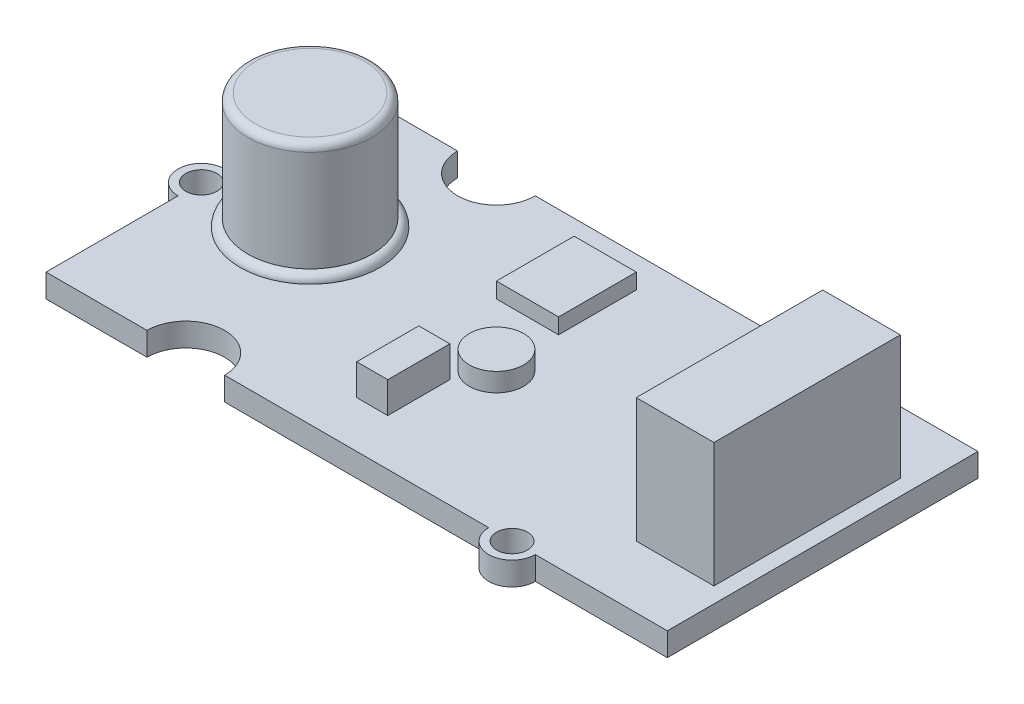
SolidWorks part; units mm, degrees
ref_plane "Front Plane" through (0, 0, 0) normal (0, 0, 1) x (1, 0, 0)
ref_plane "Top Plane" through (0, 0, 0) normal (0, 1, 0) x (1, 0, 0)
ref_plane "Right Plane" through (0, 0, 0) normal (1, 0, 0) x (0, 0, -1)
sketch "Sketch1" plane through (0, 0, 0) normal (0, 1, 0) x (1, 0, 0)
  line L1 (-20, 10) -> (20, 10)
  line L2 (-20, 10) -> (-20, -10)
  line L3 (-20, -10) -> (20, -10)
  line L4 (20, 10) -> (20, -10)
  line L5 (-20, 10) -> (20, -10) construction
  line L6 (-20, -10) -> (20, 10) construction
  point P0 (0, 0)
  dimension "D1" = 20
  dimension "D2" = 40
extrude "PCB" add sketch "Sketch1" along normal blind 1.5
sketch "Sketch3" plane through (0, 0, 0) normal (0, -1, 0) x (1, 0, 0)
  line L0 (-20, -10) -> (-20, 10) construction
  circle A0 centre (-20, 0) radius 1.5
  dimension "D1" = 3
extrude "Top mounting hole " add sketch "Sketch3" against normal blind 1.5
sketch "Sketch4" plane through (0, 0, 0) normal (0, -1, 0) x (1, 0, 0)
  circle A0 centre (-20, 0) radius 1
  dimension "D1" = 2
extrude "Top mounting hole" cut sketch "Sketch4" against normal blind 1.5
sketch "Sketch5" plane through (0, 0, 0) normal (0, -1, 0) x (1, 0, 0)
  line L0 (20, -10) -> (-20, -10) construction
  line L1 (-20, -10) -> (-20, -1.5) construction
  line L2 (-20, 10) -> (20, 10) construction
  circle A0 centre (-11, -10) radius 2.5
  circle A1 centre (-11, 10) radius 2.5
  dimension "D1" = 5
  dimension "D3" = 5
  dimension "D2" = 9
extrude "Side inlets" cut sketch "Sketch5" against normal blind 1.5
sketch "Sketch6" plane through (0, 1.5, 0) normal (0, 1, 0) x (1, 0, 0)
  line L0 (20, 10) -> (-8.5, 10) construction
  line L1 (20, -10) -> (20, 10) construction
  line L2 (-8.5, -10) -> (20, -10) construction
  circle A0 centre (10, 10) radius 1.5
  circle A2 centre (10, -10) radius 1.5
  dimension "D1" = 3
  dimension "D4" = 3
  dimension "D2" = 10
extrude "side mounting hole outline" add sketch "Sketch6" against normal blind 1.5
sketch "Sketch7" plane through (0, 1.5, 0) normal (0, 1, 0) x (1, 0, 0)
  circle A0 centre (10, 10) radius 1
  circle A1 centre (10, -10) radius 1
  dimension "D1" = 2
  dimension "D2" = 2
extrude "side mounting holes" cut sketch "Sketch7" against normal blind 1.5
sketch "Sketch8" plane through (0, 1.5, 0) normal (0, 1, 0) x (1, 0, 0)
  line L0 (-20, -10) -> (-13.5, -10) construction
  line L2 (-20, -1.5) -> (-20, -10) construction
  line L3 (-13.5, 10) -> (-20, 10) construction
  circle A0 centre (-14, 1) radius 4.5
  dimension "D1" = 11
  dimension "D2" = 9
  dimension "D3" = 6
  dimension "D4" = 9
extrude "sensor base" add sketch "Sketch8" along normal blind 0.5
sketch "Sketch9" plane through (0, 2, 0) normal (0, 1, 0) x (1, 0, 0)
  circle A0 centre (-14, 1) radius 4
  dimension "D1" = 8
extrude "sensor" add sketch "Sketch9" along normal blind 7
fillet "sensor fillet" radius 0.5 2 edges at (-14, 9, 3) (-14, 2, 3.5)
sketch "Sketch10" plane through (0, 1.5, 0) normal (0, 1, 0) x (1, 0, 0)
  line L0 (11.5, -10) -> (20, -10) construction
  line L1 (14, 6) -> (19, 6)
  line L2 (14, 6) -> (14, -6)
  line L3 (14, -6) -> (19, -6)
  line L4 (19, 6) -> (19, -6)
  line L5 (14, 6) -> (19, -6) construction
  line L6 (14, -6) -> (19, 6) construction
  line L7 (20, 10) -> (11.5, 10) construction
  line L8 (20, -10) -> (20, 10) construction
  point P0 (16.5, 0)
  dimension "D1" = 4
  dimension "D2" = 12
  dimension "D3" = 4
  dimension "D4" = 5
  dimension "D5" = 1
extrude "connector" add sketch "Sketch10" along normal blind 8
sketch "Sketch11" plane through (0, 1.5, 0) normal (0, 1, 0) x (1, 0, 0)
  line L0 (20, -10) -> (20, 10) construction
  line L1 (-4, 8) -> (0, 8)
  line L2 (-4, 8) -> (-4, 3)
  line L3 (-4, 3) -> (0, 3)
  line L4 (0, 8) -> (0, 3)
  line L5 (-4, 8) -> (0, 3) construction
  line L6 (-4, 3) -> (0, 8) construction
  line L7 (8.5, 10) -> (-8.5, 10) construction
  point P0 (-2, 5.5)
  dimension "D1" = 4
  dimension "D2" = 5
  dimension "D3" = 20
  dimension "D4" = 2
extrude "chip" add sketch "Sketch11" along normal blind 1
sketch "Sketch12" plane through (0, 1.5, 0) normal (0, 1, 0) x (1, 0, 0)
  line L0 (8.5, 10) -> (-8.5, 10) construction
  line L1 (20, -10) -> (20, 10) construction
  circle A0 centre (0, -1) radius 1.75
  dimension "D1" = 3.5
  dimension "D2" = 11
  dimension "D3" = 20
extrude "Boss-Extrude10" add sketch "Sketch12" along normal blind 1.2
sketch "Sketch13" plane through (0, 1.5, 0) normal (0, 1, 0) x (1, 0, 0)
  line L0 (20, -10) -> (20, 10) construction
  line L1 (-3, -3) -> (-1, -3)
  line L2 (-3, -3) -> (-3, -7)
  line L3 (-3, -7) -> (-1, -7)
  line L4 (-1, -3) -> (-1, -7)
  line L5 (-3, -3) -> (-1, -7) construction
  line L6 (-3, -7) -> (-1, -3) construction
  line L7 (-8.5, -10) -> (8.5, -10) construction
  point P0 (-2, -5)
  dimension "D1" = 2
  dimension "D2" = 4
  dimension "D3" = 21
  dimension "D4" = 3
extrude "Boss-Extrude11" add sketch "Sketch13" along normal blind 2
